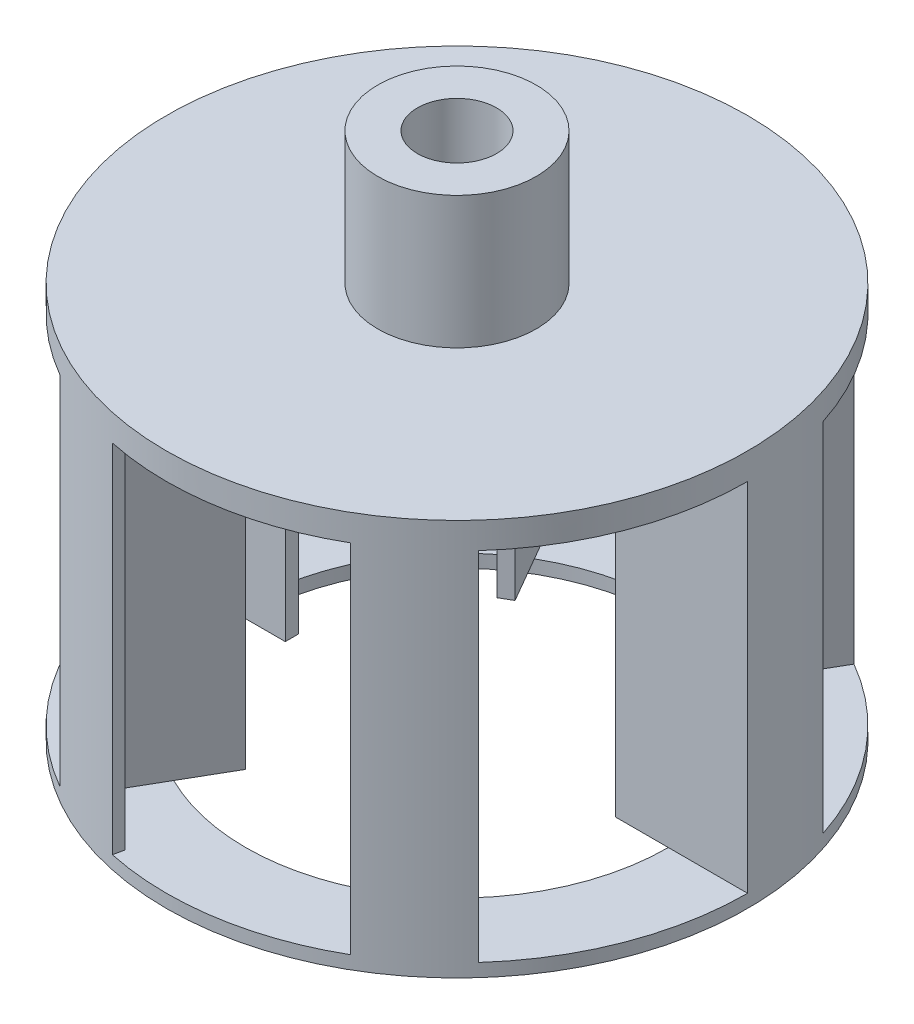
SolidWorks part; units mm, degrees
ref_plane "Front Plane" through (0, 0, 0) normal (0, 0, 1) x (1, 0, 0)
ref_plane "Top Plane" through (0, 0, 0) normal (0, 1, 0) x (1, 0, 0)
ref_plane "Right Plane" through (0, 0, 0) normal (1, 0, 0) x (0, 0, -1)
sketch "Sketch1" plane through (0, 0, 0) normal (0, 1, 0) x (1, 0, 0)
  line L0 (55, 0) -> (30, 0)
  line L1 (30, 0) -> (30, 2.5)
  line L2 (30, 2.5) -> (52.941, 2.5)
  line L3 (50.406, 16.3779) -> (52.3081, 16.9959)
  line L4 (27.5, -47.6314) -> (15, -25.9808)
  line L5 (15, -25.9808) -> (17.1651, -24.7308)
  line L6 (17.1651, -24.7308) -> (28.6356, -44.5983)
  line L7 (39.3867, -35.4639) -> (40.873, -36.8022)
  line L8 (-27.5, -47.6314) -> (-15, -25.9808)
  line L9 (-15, -25.9808) -> (-12.8349, -27.2308)
  line L10 (-12.8349, -27.2308) -> (-24.3054, -47.0983)
  line L11 (-11.0193, -51.8418) -> (-11.4351, -53.7981)
  line L12 (-55, 0) -> (-30, 0)
  line L13 (-30, 0) -> (-30, -2.5)
  line L14 (-30, -2.5) -> (-52.941, -2.5)
  line L15 (-50.406, -16.3779) -> (-52.3081, -16.9959)
  line L16 (-27.5, 47.6314) -> (-15, 25.9808)
  line L17 (-15, 25.9808) -> (-17.1651, 24.7308)
  line L18 (-17.1651, 24.7308) -> (-28.6356, 44.5983)
  line L19 (-39.3867, 35.4639) -> (-40.873, 36.8022)
  line L20 (27.5, 47.6314) -> (15, 25.9808)
  line L21 (15, 25.9808) -> (12.8349, 27.2308)
  line L22 (12.8349, 27.2308) -> (24.3054, 47.0983)
  line L23 (11.0193, 51.8418) -> (11.4351, 53.7981)
  arc A0 (55, 0) -> (52.3081, 16.9959) centre (0, 0) ccw
  arc A1 (52.941, 2.5) -> (50.406, 16.3779) centre (0, 0) ccw
  arc A2 (27.5, -47.6314) -> (40.873, -36.8022) centre (0, 0) ccw
  arc A3 (28.6356, -44.5983) -> (39.3867, -35.4639) centre (0, 0) ccw
  arc A4 (-27.5, -47.6314) -> (-11.4351, -53.7981) centre (0, 0) ccw
  arc A5 (-24.3054, -47.0983) -> (-11.0193, -51.8418) centre (0, 0) ccw
  arc A6 (-55, 0) -> (-52.3081, -16.9959) centre (0, 0) ccw
  arc A7 (-52.941, -2.5) -> (-50.406, -16.3779) centre (0, 0) ccw
  arc A8 (-27.5, 47.6314) -> (-40.873, 36.8022) centre (0, 0) ccw
  arc A9 (-28.6356, 44.5983) -> (-39.3867, 35.4639) centre (0, 0) ccw
  arc A10 (27.5, 47.6314) -> (11.4351, 53.7981) centre (0, 0) ccw
  arc A11 (24.3054, 47.0983) -> (11.0193, 51.8418) centre (0, 0) ccw
  point P40 (0, 0)
  dimension "D1" = 110
  dimension "D2" = 2.5
  dimension "D6" = 6
  dimension "D3" = 2
  dimension "D4" = 18
  dimension "D5" = 25
extrude "Boss-Extrude1" add sketch "Sketch1" along normal blind 67.5
sketch "Sketch2" plane through (0, 0, 0) normal (0, 1, 0) x (1, 0, 0)
  circle A0 centre (0, 0) radius 55
  circle A1 centre (0, 0) radius 40
  dimension "D1" = 110
  dimension "D2" = 80
extrude "Boss-Extrude2" add sketch "Sketch2" against normal blind 2.5
sketch "Sketch3" plane through (0, 0, 0) normal (0, 1, 0) x (1, 0, 0)
  circle A0 centre (0, 0) radius 7.5
  circle A1 centre (0, 0) radius 55
  dimension "D1" = 15
  dimension "D2" = 110
extrude "Boss-Extrude3" add sketch "Sketch3" along normal blind 5 from offset 67.5
sketch "Sketch4" plane through (0, 72.5, 0) normal (0, 1, 0) x (1, 0, 0)
  circle A0 centre (0, 0) radius 15
  circle A1 centre (0, 0) radius 7.5
  dimension "D1" = 30
  dimension "D2" = 15
extrude "Boss-Extrude4" add sketch "Sketch4" along normal blind 25
